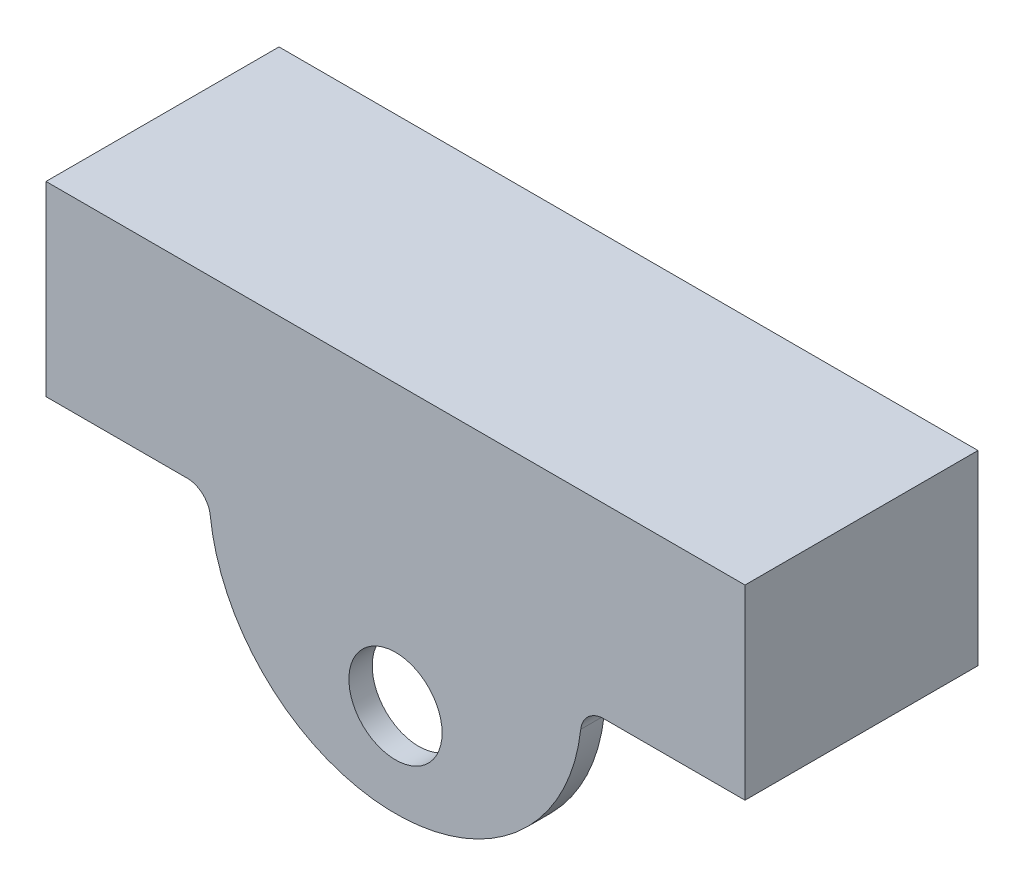
SolidWorks part; units mm, degrees
ref_plane "Front Plane" through (0, 0, 0) normal (0, 0, 1) x (1, 0, 0)
ref_plane "Top Plane" through (0, 0, 0) normal (0, 1, 0) x (1, 0, 0)
ref_plane "Right Plane" through (0, 0, 0) normal (1, 0, 0) x (0, 0, -1)
sketch "Sketch1" plane through (0, 0, 0) normal (0, 0, 1) x (1, 0, 0)
  line L0 (-75, 0) -> (75, 0)
  line L1 (75, 0) -> (75, -40)
  line L2 (75, -40) -> (-75, -40)
  line L3 (-75, -40) -> (-75, 0)
  arc A0 (-40, -40) -> (40, -40) centre (0, -40) ccw
  circle A2 centre (0, -60) radius 10
  point P3 (0, -62.8931)
  point P4 (0, 0)
  dimension "D3" = 80
  dimension "D4" = 20
  dimension "D1" = 40
  dimension "D2" = 150
  dimension "D5" = 40
  dimension "D6" = 20
extrude "Boss-Extrude1" add sketch "Sketch1" along normal blind 50 contours L3 L2 L1 L0 | L2 A0 | A2 region at (0, -20, 0) region at (0, -40.8944, 0)
shell "Shell2" thickness 5 removed face at (57.5, -40, 25) removed face at (0, -60, 25) removed face at (-57.5, -40, 25)
fillet "Fillet1" radius 5 4 edges at (40, -40, 2.5) (40, -40, 47.5) (-40, -40, 2.5) (-40, -40, 47.5)
extrude "Cut-Extrude2" cut sketch "Sketch1<4>" against normal through all and the other way through all contours A2 region at (0, -60, 0)
sketch "Sketch1<4>" plane through (0, 0, 0) normal (0, 0, 1) x (1, 0, 0) same geometry as "Sketch1"
